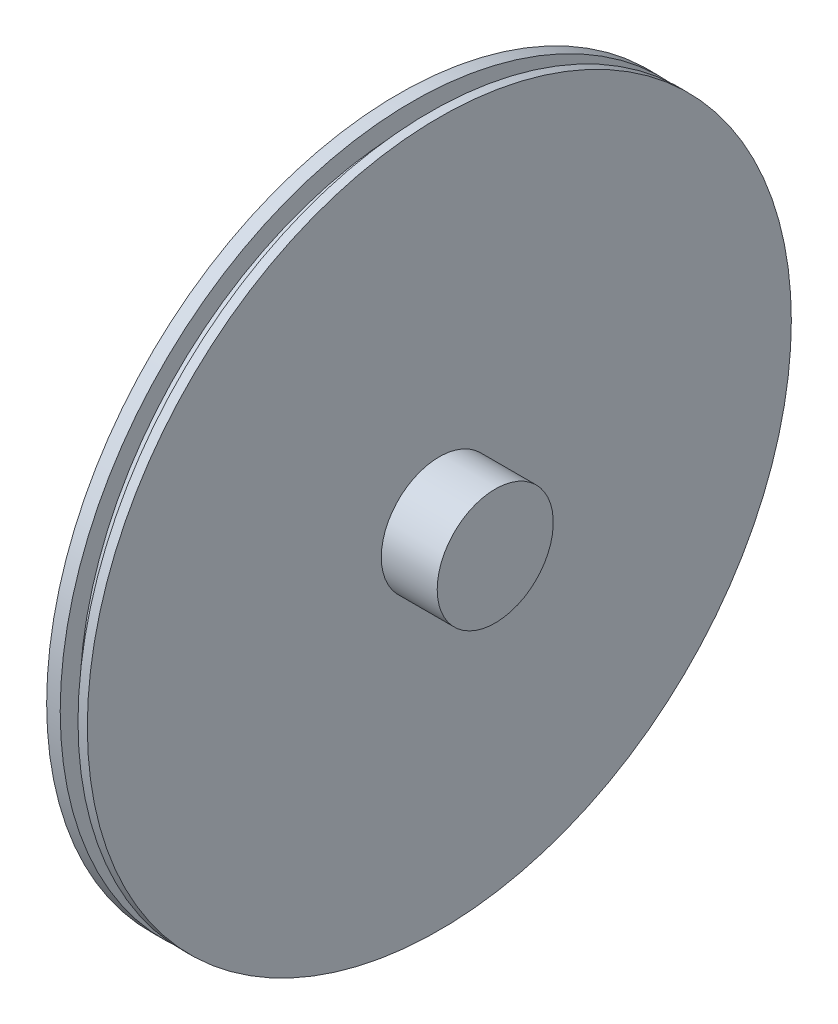
SolidWorks part; units mm, degrees
ref_plane "Płaszczyzna przednia" through (0, 0, 0) normal (0, 0, 1) x (1, 0, 0)
ref_plane "Płaszczyzna górna" through (0, 0, 0) normal (0, 1, 0) x (1, 0, 0)
ref_plane "Płaszczyzna prawa" through (0, 0, 0) normal (1, 0, 0) x (0, 0, -1)
sketch "Szkic1" plane through (0, 0, 0) normal (0, 0, 1) x (1, 0, 0)
  line L0 (0, 0) -> (21.5656, 0)
  line L1 (21.5656, 0) -> (21.5656, 16.4142)
  line L2 (21.5656, 16.4142) -> (5.7559, 16.4142)
  line L3 (5.7559, 16.4142) -> (5.7559, 99.5632)
  line L4 (5.7559, 99.5632) -> (3.1201, 99.5632)
  line L5 (3.1201, 99.5632) -> (3.1201, 94.0519)
  line L6 (3.1201, 94.0519) -> (-1.912, 94.0519)
  line L7 (-1.912, 94.0519) -> (-1.912, 99.5632)
  line L8 (-1.912, 99.5632) -> (-5.7459, 99.5632)
  line L9 (-5.7459, 99.5632) -> (-5.7459, 0)
  line L10 (-5.7459, 0) -> (0, 0)
revolve "Obrót1" add sketch "Szkic1" angle 360 about L0
